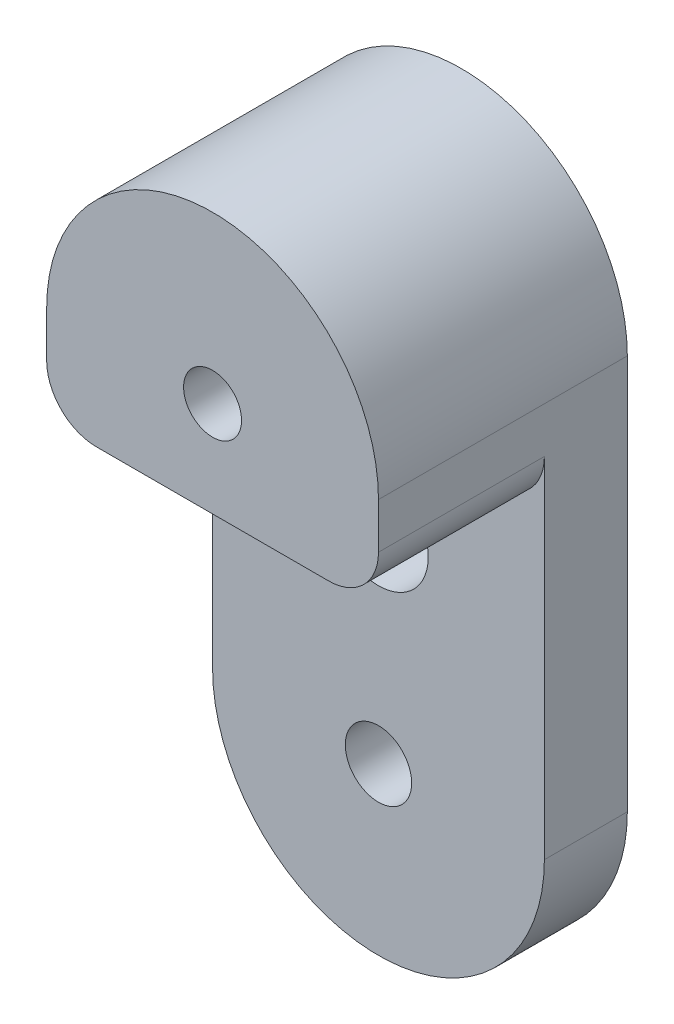
SolidWorks part; units mm, degrees
ref_plane "Front Plane" through (0, 0, 0) normal (0, 0, 1) x (1, 0, 0)
ref_plane "Top Plane" through (0, 0, 0) normal (0, 1, 0) x (1, 0, 0)
ref_plane "Right Plane" through (0, 0, 0) normal (1, 0, 0) x (0, 0, -1)
sketch "Sketch1" plane through (0, 0, 0) normal (0, 0, 1) x (1, 0, 0)
  line L0 (0, 0) -> (0, -23.8) construction
  line L1 (10, 0) -> (10, -23.8)
  line L2 (-10, 0) -> (-10, -23.8)
  line L3 (-10, -5.75) -> (10, -5.75)
  circle A0 centre (0, 0) radius 1.7462
  circle A1 centre (0, -11.5) radius 3
  circle A2 centre (0, -23.8) radius 2
  arc A3 (10, 0) -> (-10, 0) centre (0, 0) ccw
  arc A4 (-10, -23.8) -> (10, -23.8) centre (0, -23.8) ccw
  point P7 (0, -11.9)
  point P14 (0, -12.65)
  point P15 (-1.9132, -12.8584)
  dimension "D1" = 4
  dimension "D2" = 6
  dimension "D3" = 3.4925
  dimension "D4" = 11.5
  dimension "D5" = 7.3
  dimension "D6" = 20
  dimension "D7" = 11.5
  dimension "D8" = 5.75
extrude "Boss-Extrude1" add sketch "Sketch1" along normal blind 5 contours L2 A4 L1 L3 A1 A2 region at (0, -19.0988, 0)
extrude "Boss-Extrude2" add sketch "Sketch1<3>" along normal blind 15 contours A0 L3 L1 A3 L2 region at (9.7454, -2.875, 0)
sketch "Sketch1<3>" plane through (0, 0, 0) normal (0, 0, 1) x (1, 0, 0) same geometry as "Sketch1"
fillet "Fillet1" radius 3 2 edges at (10, -5.75, 10) (-10, -5.75, 10)
equation "\"D8@Sketch1\"=\"D7@Sketch1\"/2"
equation "\"D3@Sketch1\"=0.125*25.4*1.1"
